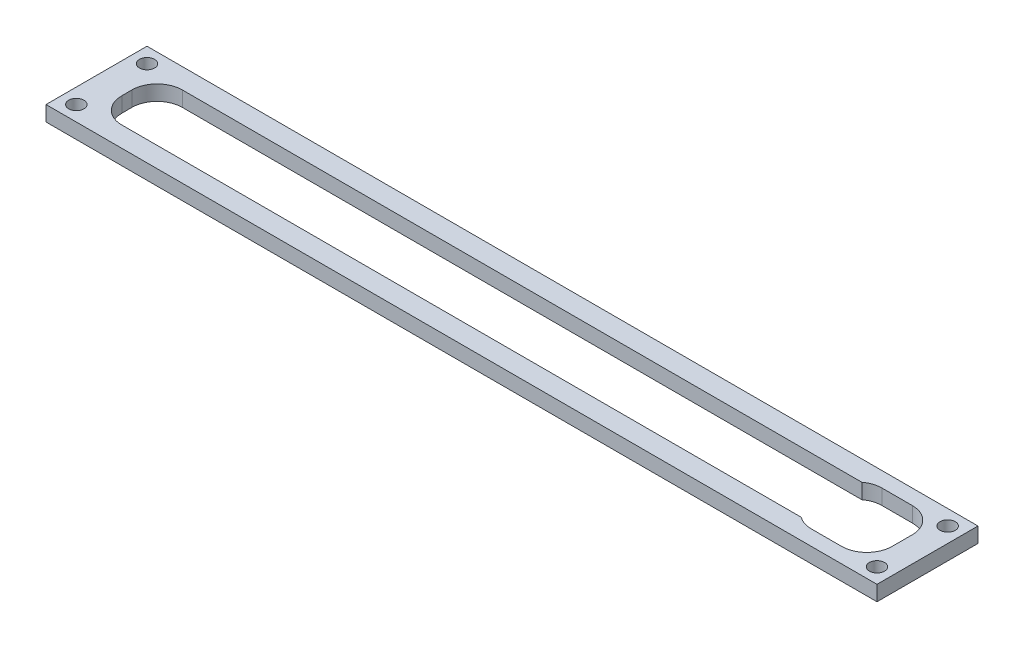
SolidWorks part; units mm, degrees
ref_plane "Front Plane" through (0, 0, 0) normal (0, 0, 1) x (1, 0, 0)
ref_plane "Top Plane" through (0, 0, 0) normal (0, 1, 0) x (1, 0, 0)
ref_plane "Right Plane" through (0, 0, 0) normal (1, 0, 0) x (0, 0, -1)
sketch "Sketch1" plane through (0, 0, 0) normal (0, 1, 0) x (1, 0, 0)
  line L0 (82.2674, 20) -> (82.2674, 0) construction
  line L1 (0, 0) -> (164.5348, 0)
  line L2 (0, 0) -> (0, 20)
  line L3 (0, 20) -> (164.5348, 20)
  line L4 (164.5348, 0) -> (164.5348, 20)
  line L5 (0, 10) -> (164.5348, 10) construction
  line L6 (82.2674, 16) -> (82.2674, 4) construction
  line L7 (6, 16) -> (158.5348, 16)
  line L8 (6, 16) -> (6, 4)
  line L9 (6, 4) -> (158.5348, 4)
  line L10 (158.5348, 16) -> (158.5348, 4)
  line L11 (6, 10) -> (158.5348, 10) construction
  circle A0 centre (3, 17) radius 1.5
  circle A1 centre (3, 3) radius 1.5
  circle A2 centre (161.5348, 3) radius 1.5
  circle A3 centre (161.5348, 17) radius 1.5
  point P17 (82.2674, 10)
  point P18 (82.2674, 10)
  dimension "D7" = 3
  dimension "D1" = 164.5348
  dimension "D2" = 20
  dimension "D3" = 152.5348
  dimension "D4" = 12
  dimension "D5" = 3
  dimension "D6" = 3
extrude "Boss-Extrude1" add sketch "Sketch1" along normal blind 3
sketch "Sketch2" plane through (0, 3, 0) normal (0, 1, 0) x (1, 0, 0)
  line L0 (92, 10) -> (-49908, 10) construction
  line L1 (158.5348, 4) -> (158.5348, 16) construction
  line L2 (145.5348, 17) -> (145.5348, 16)
  line L5 (158.5348, 16) -> (6, 16) construction
  line L6 (152.5348, 17) -> (152.5348, 3) construction
  line L7 (145.5348, 17) -> (159.5348, 17)
  line L9 (145.5348, 3) -> (159.5348, 3)
  line L10 (159.5348, 17) -> (159.5348, 3)
  line L12 (145.5348, 16) -> (158.5348, 16)
  line L13 (158.5348, 16) -> (158.5348, 4)
  line L14 (158.5348, 4) -> (145.5348, 4)
  line L15 (6, 4) -> (158.5348, 4) construction
  line L16 (145.5348, 4) -> (145.5348, 3)
  point P4 (158.5348, 10)
  point P23 (152.5348, 10)
  dimension "D1" = 1
  dimension "D2" = 14
  dimension "D3" = 14
extrude "Cut-Extrude1" cut sketch "Sketch2" against normal through all
fillet "Fillet1" radius 5 6 edges at (159.5348, 1.5, -17) (159.5348, 1.5, -3) (145.5348, 1.5, -17) (145.5348, 1.5, -3) (6, 1.5, -4) (6, 1.5, -16)
equation "\"TrackLength\"= ( ( \"n\" * 28 ) ) / cos ( \"MountAngle\" ) - ( 2 * \"x\" )"
equation "\"D1@Sketch1\"=\"TrackLength\""
equation "\"TrackWidth\"= \"MarbleTrackWidth\" + ( 2 * 4 )"
equation "\"D2@Sketch1\"=\"TrackWidth\""
equation "\"MarbleTrackWidth\"= \"MarbleWidth\" - 1"
equation "\"MarbleTrackLength\"= \"TrackLength\" - ( 2 * 6 )"
equation "\"D3@Sketch1\"=\"MarbleTrackLength\""
equation "\"D4@Sketch1\"=\"MarbleTrackWidth\""
equation "\"MarbleWidth\"= 13"
equation "\"n\"= 6"
equation "\"MountAngle\"= 5"
equation "\"x\"= 14 / cos ( \"MountAngle\" ) - 12"
